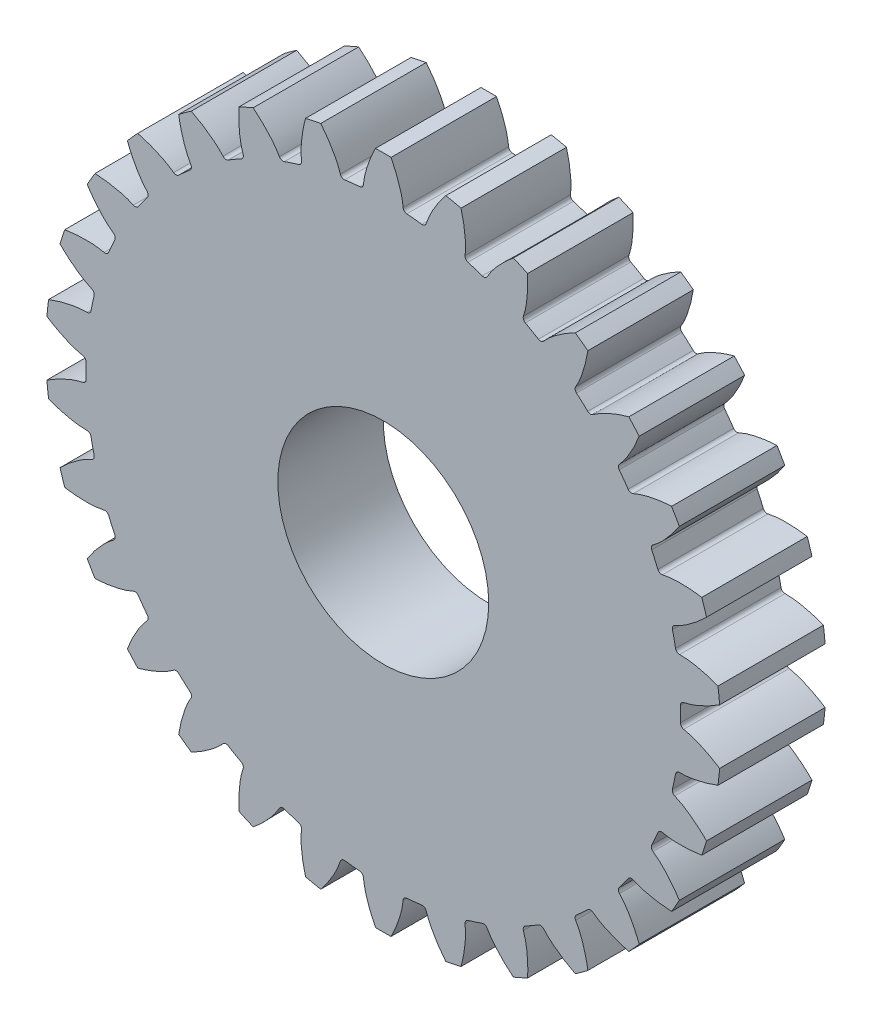
SolidWorks part; units mm, degrees
ref_plane "前视基准面" through (0, 0, 0) normal (0, 0, 1) x (1, 0, 0)
ref_plane "上视基准面" through (0, 0, 0) normal (0, 1, 0) x (1, 0, 0)
ref_plane "右视基准面" through (0, 0, 0) normal (1, 0, 0) x (0, 0, -1)
other "Configuration Table"
sketch "circles" plane through (0, 0, 0) normal (0, 0, 1) x (1, 0, 0)
  circle A0 centre (0, 0) radius 32
  circle A1 centre (0, 0) radius 27.5
  circle A2 centre (0, 0) radius 28.1908
  circle A3 centre (0, 0) radius 30
  dimension "D1" = 60
  dimension "D2" = 56.3816
  dimension "D3" = 55
  dimension "D4" = 64
extrude "Gear_extrude" add sketch "circles" along normal blind 10 contours A0
sketch "Involute" plane through (0, 0, 10) normal (0, 0, 1) x (1, 0, 0)
  spline S0 degree 4 poles (28.171, -1.0557) (28.2223, -1.0593) (28.3658, -1.0748) (28.6344, -1.1247) (29.0665, -1.2353) (29.6059, -1.4183) (30.2862, -1.7021) (31.0629, -2.0956) (31.8862, -2.5882) (32.9602, -3.3359) (34.1728, -4.337) (35.451, -5.5998) (36.7769, -7.1739) (37.9681, -8.8517) (39.0285, -10.6149) (39.9764, -12.4839) (40.7958, -14.4124) (41.4038, -16.142) (41.8493, -17.6484) (42.1713, -18.9171) (42.3998, -19.9389) (42.6495, -21.2237) (42.8522, -22.517) (43.0089, -23.8165) (43.1207, -25.1207) (43.1836, -26.1655) (43.2157, -27.0819) (43.2272, -27.8657) (43.226, -28.5232) (43.2194, -29.0333) (43.2013, -29.7091) (43.1793, -30.2472) (43.1275, -31.2203) (43.075, -31.832) (43.0114, -32.5795) (42.9682, -32.9515) (42.9431, -33.1951) (42.9309, -33.297) knots 0 0 0 0 0 0.005377 0.015084 0.028532 0.04661 0.064855 0.092111 0.119476 0.146842 0.201575 0.256307 0.307035 0.361767 0.4165 0.471232 0.525964 0.580697 0.608063 0.635429 0.662795 0.690161 0.744894 0.77226 0.799626 0.826992 0.854358 0.868042 0.881725 0.895408 0.909091 0.931818 0.954545 0.977273 0.988636 1 1 1 1 1 construction
  spline S2 degree 4 poles (28.171, 1.0557) (28.2223, 1.0593) (28.3658, 1.0748) (28.6344, 1.1247) (29.0665, 1.2353) (29.6059, 1.4183) (30.2862, 1.7021) (31.0629, 2.0956) (31.8862, 2.5882) (32.9602, 3.3359) (34.1728, 4.337) (35.451, 5.5998) (36.7769, 7.1739) (37.9681, 8.8517) (39.0285, 10.6149) (39.9764, 12.4839) (40.7958, 14.4124) (41.4038, 16.142) (41.8493, 17.6484) (42.1713, 18.9171) (42.3998, 19.9389) (42.6495, 21.2237) (42.8522, 22.517) (43.0089, 23.8165) (43.1207, 25.1207) (43.1836, 26.1655) (43.2157, 27.0819) (43.2272, 27.8657) (43.226, 28.5232) (43.2194, 29.0333) (43.2013, 29.7091) (43.1793, 30.2472) (43.1275, 31.2203) (43.075, 31.832) (43.0114, 32.5795) (42.9682, 32.9515) (42.9431, 33.1951) (42.9309, 33.297) knots 0 0 0 0 0 0.005377 0.015084 0.028532 0.04661 0.064855 0.092111 0.119476 0.146842 0.201575 0.256307 0.307035 0.361767 0.4165 0.471232 0.525964 0.580697 0.608063 0.635429 0.662795 0.690161 0.744894 0.77226 0.799626 0.826992 0.854358 0.868042 0.881725 0.895408 0.909091 0.931818 0.954545 0.977273 0.988636 1 1 1 1 1 construction
  spline S3 degree 4 poles (28.171, 1.0557) (28.2223, 1.0593) (28.3658, 1.0748) (28.6344, 1.1247) (29.0665, 1.2353) (29.6059, 1.4183) (30.2862, 1.7021) (31.0629, 2.0956) (31.8862, 2.5882) (32.9602, 3.3359) (34.1728, 4.337) (35.451, 5.5998) (36.7769, 7.1739) (37.9681, 8.8517) (39.0285, 10.6149) (39.9764, 12.4839) (40.7958, 14.4124) (41.4038, 16.142) (41.8493, 17.6484) (42.1713, 18.9171) (42.3998, 19.9389) (42.6495, 21.2237) (42.8522, 22.517) (43.0089, 23.8165) (43.1207, 25.1207) (43.1836, 26.1655) (43.2157, 27.0819) (43.2272, 27.8657) (43.226, 28.5232) (43.2194, 29.0333) (43.2078, 29.4683) (43.1997, 29.7103) (43.1953, 29.8292) knots 0 0 0 0 0 0.005377 0.015084 0.028532 0.04661 0.064855 0.092111 0.119476 0.146842 0.201575 0.256307 0.307035 0.361767 0.4165 0.471232 0.525964 0.580697 0.608063 0.635429 0.662795 0.690161 0.744894 0.77226 0.799626 0.826992 0.854358 0.868042 0.881725 0.895408 0.909091 0.909091 0.909091 0.909091 0.909091
  spline S4 degree 4 poles (28.171, -1.0557) (28.2223, -1.0593) (28.3658, -1.0748) (28.6344, -1.1247) (29.0665, -1.2353) (29.6059, -1.4183) (30.2862, -1.7021) (31.0629, -2.0956) (31.8862, -2.5882) (32.9602, -3.3359) (34.1728, -4.337) (35.451, -5.5998) (36.7769, -7.1739) (37.9681, -8.8517) (39.0285, -10.6149) (39.9764, -12.4839) (40.7958, -14.4124) (41.4038, -16.142) (41.8493, -17.6484) (42.1713, -18.9171) (42.3998, -19.9389) (42.6495, -21.2237) (42.8522, -22.517) (43.0089, -23.8165) (43.1207, -25.1207) (43.1836, -26.1655) (43.2157, -27.0819) (43.2272, -27.8657) (43.226, -28.5232) (43.2194, -29.0333) (43.2078, -29.4683) (43.1997, -29.7103) (43.1953, -29.8292) knots 0 0 0 0 0 0.005377 0.015084 0.028532 0.04661 0.064855 0.092111 0.119476 0.146842 0.201575 0.256307 0.307035 0.361767 0.4165 0.471232 0.525964 0.580697 0.608063 0.635429 0.662795 0.690161 0.744894 0.77226 0.799626 0.826992 0.854358 0.868042 0.881725 0.895408 0.909091 0.909091 0.909091 0.909091 0.909091
sketch "Db>Df" plane through (0, 0, 10) normal (0, 0, 1) x (1, 0, 0)
  line L2 (0, 0) -> (29.9589, 1.5701) construction
  line L3 (0, 0) -> (60.2478, -1.5776) construction
  line L4 (43.1953, 29.8292) -> (60.2478, -1.5776)
  line L5 (60.2478, -1.5776) -> (43.1953, -29.8292)
  circle A2 centre (0, 0) radius 30 construction
  circle A3 centre (0, 0) radius 28.1908 construction
  arc A4 (28.171, -1.0557) -> (28.171, 1.0557) centre (0, 0) ccw
  spline S0 degree 4 poles (-58.7454, -1999.1168) (17.076, -52.2104) (22.5891, -1.8433) (25.9954, -0.4491) (29.0665, -1.2353) (29.6059, -1.4183) (30.2862, -1.7021) (31.0629, -2.0956) (31.8862, -2.5882) (32.9602, -3.3359) (34.1728, -4.337) (35.451, -5.5998) (36.7769, -7.1739) (37.9681, -8.8517) (39.0285, -10.6149) (39.9764, -12.4839) (40.7958, -14.4124) (41.4038, -16.142) (41.8493, -17.6484) (42.1713, -18.9171) (42.3998, -19.9389) (42.6495, -21.2237) (42.8522, -22.517) (43.0089, -23.8165) (43.1207, -25.1207) (43.1836, -26.1655) (43.2157, -27.0819) (43.2272, -27.8657) (43.226, -28.5232) (43.1903, -31.2711) (42.8434, -36.3545) (44.7406, 23.1759) (-32.5965, -2028.0551) knots -0.284666 -0.284666 -0.284666 -0.284666 -0.284666 0.005377 0.015084 0.028532 0.04661 0.064855 0.092111 0.119476 0.146842 0.201575 0.256307 0.307035 0.361767 0.4165 0.471232 0.525964 0.580697 0.608063 0.635429 0.662795 0.690161 0.744894 0.77226 0.799626 0.826992 0.854358 0.868042 0.881725 0.895408 1.149228 1.149228 1.149228 1.149228 1.149228 only from (28.171, -1.0557) to (43.1953, -29.8292) construction
  spline S1 degree 4 poles (-58.7454, 1999.1168) (17.076, 52.2104) (22.5891, 1.8433) (25.9954, 0.4491) (29.0665, 1.2353) (29.6059, 1.4183) (30.2862, 1.7021) (31.0629, 2.0956) (31.8862, 2.5882) (32.9602, 3.3359) (34.1728, 4.337) (35.451, 5.5998) (36.7769, 7.1739) (37.9681, 8.8517) (39.0285, 10.6149) (39.9764, 12.4839) (40.7958, 14.4124) (41.4038, 16.142) (41.8493, 17.6484) (42.1713, 18.9171) (42.3998, 19.9389) (42.6495, 21.2237) (42.8522, 22.517) (43.0089, 23.8165) (43.1207, 25.1207) (43.1836, 26.1655) (43.2157, 27.0819) (43.2272, 27.8657) (43.226, 28.5232) (43.1903, 31.2711) (42.8434, 36.3545) (44.7406, -23.1759) (-32.5965, 2028.0551) knots -0.284666 -0.284666 -0.284666 -0.284666 -0.284666 0.005377 0.015084 0.028532 0.04661 0.064855 0.092111 0.119476 0.146842 0.201575 0.256307 0.307035 0.361767 0.4165 0.471232 0.525964 0.580697 0.608063 0.635429 0.662795 0.690161 0.744894 0.77226 0.799626 0.826992 0.854358 0.868042 0.881725 0.895408 1.149228 1.149228 1.149228 1.149228 1.149228 only from (28.171, 1.0557) to (43.1953, 29.8292) construction
  spline S2 degree 4 poles (28.171, -1.0557) (28.2223, -1.0593) (28.3658, -1.0748) (28.6344, -1.1247) (29.0665, -1.2353) (29.6059, -1.4183) (30.2862, -1.7021) (31.0629, -2.0956) (31.8862, -2.5882) (32.9602, -3.3359) (34.1728, -4.337) (35.451, -5.5998) (36.7769, -7.1739) (37.9681, -8.8517) (39.0285, -10.6149) (39.9764, -12.4839) (40.7958, -14.4124) (41.4038, -16.142) (41.8493, -17.6484) (42.1713, -18.9171) (42.3998, -19.9389) (42.6495, -21.2237) (42.8522, -22.517) (43.0089, -23.8165) (43.1207, -25.1207) (43.1836, -26.1655) (43.2157, -27.0819) (43.2272, -27.8657) (43.226, -28.5232) (43.2194, -29.0333) (43.2078, -29.4683) (43.1997, -29.7103) (43.1953, -29.8292) knots 0 0 0 0 0 0.005377 0.015084 0.028532 0.04661 0.064855 0.092111 0.119476 0.146842 0.201575 0.256307 0.307035 0.361767 0.4165 0.471232 0.525964 0.580697 0.608063 0.635429 0.662795 0.690161 0.744894 0.77226 0.799626 0.826992 0.854358 0.868042 0.881725 0.895408 0.909091 0.909091 0.909091 0.909091 0.909091
  spline S3 degree 4 poles (28.171, 1.0557) (28.2223, 1.0593) (28.3658, 1.0748) (28.6344, 1.1247) (29.0665, 1.2353) (29.6059, 1.4183) (30.2862, 1.7021) (31.0629, 2.0956) (31.8862, 2.5882) (32.9602, 3.3359) (34.1728, 4.337) (35.451, 5.5998) (36.7769, 7.1739) (37.9681, 8.8517) (39.0285, 10.6149) (39.9764, 12.4839) (40.7958, 14.4124) (41.4038, 16.142) (41.8493, 17.6484) (42.1713, 18.9171) (42.3998, 19.9389) (42.6495, 21.2237) (42.8522, 22.517) (43.0089, 23.8165) (43.1207, 25.1207) (43.1836, 26.1655) (43.2157, 27.0819) (43.2272, 27.8657) (43.226, 28.5232) (43.2194, 29.0333) (43.2078, 29.4683) (43.1997, 29.7103) (43.1953, 29.8292) knots 0 0 0 0 0 0.005377 0.015084 0.028532 0.04661 0.064855 0.092111 0.119476 0.146842 0.201575 0.256307 0.307035 0.361767 0.4165 0.471232 0.525964 0.580697 0.608063 0.635429 0.662795 0.690161 0.744894 0.77226 0.799626 0.826992 0.854358 0.868042 0.881725 0.895408 0.909091 0.909091 0.909091 0.909091 0.909091
  dimension "D1" = 4.5
  dimension "D2" = 60
extrude "extruded-cut1" cut sketch "Db>Df" against normal through all
fillet "fillet1" radius 0.38 2 edges at (28.171, -1.0557, 5) (28.171, 1.0557, 5)
pattern_circular "circular-parttern1" count 30 over 360 about axis through (0, 0, 10) along (0, 0, -1) of "extruded-cut1", "fillet1" reverse direction yes
sketch "Db<Df" [suppressed] plane through (0, 0, 10) normal (0, 0, 1) x (1, 0, 0)
  line L0 (0, 0) -> (100.8439, 0) construction
  line L1 (0, 0) -> (49.9753, 1.5705) construction
  line L2 (73.0175, 48.1968) -> (100.8439, 0)
  line L3 (100.8439, 0) -> (73.0175, -48.1968)
  circle A0 centre (0, 0) radius 47.5 construction
  arc A1 (47.4927, -0.8355) -> (47.4927, 0.8355) centre (0, 0) ccw
  circle A2 centre (0, 0) radius 50 construction
  spline S0 degree 4 poles (69.1798, -1998.5936) (37.8966, 59.197) (41.8514, 1.7937) (44.8419, 0.3903) (47.7946, 0.8837) (48.4767, 1.0444) (49.3818, 1.3297) (50.5254, 1.7793) (51.8333, 2.4075) (53.2224, 3.1999) (54.6746, 4.1663) (56.0658, 5.2211) (57.3956, 6.3522) (58.6648, 7.5507) (60.1325, 9.0778) (61.7919, 11.0209) (63.5752, 13.4244) (65.4038, 16.3254) (67.0485, 19.4065) (68.4812, 22.5914) (69.5546, 25.4522) (70.3495, 27.9469) (70.9303, 30.0495) (71.3467, 31.7445) (71.7156, 33.4497) (72.0375, 35.1657) (72.3133, 36.8876) (72.5435, 38.6195) (72.7289, 40.3511) (72.8524, 41.8792) (72.9313, 43.1759) (72.9787, 44.2811) (73.0067, 45.1233) (73.0226, 46.0516) (73.0565, 49.344) (72.7733, 58.0548) (73.7264, -18.7455) (39.1601, 2047.4863) knots -0.159153 -0.159153 -0.159153 -0.159153 -0.159153 0.002688 0.005377 0.015084 0.028532 0.04661 0.064855 0.092111 0.119476 0.146842 0.174209 0.201575 0.228941 0.256307 0.307035 0.361767 0.4165 0.471232 0.525964 0.580697 0.608063 0.635429 0.662795 0.690161 0.717528 0.744894 0.77226 0.799626 0.826992 0.840675 0.854358 0.868042 0.881725 0.895408 1.086914 1.086914 1.086914 1.086914 1.086914 only from (46.9782, 0.7758) to (73.0175, 48.1968) construction
  spline S1 degree 4 poles (47.4927, 0.8355) (47.602, 0.8537) (47.9217, 0.9139) (48.5186, 1.0576) (49.3818, 1.3297) (50.5254, 1.7793) (51.8333, 2.4075) (53.2224, 3.1999) (54.6746, 4.1663) (56.0658, 5.2211) (57.3956, 6.3522) (58.6648, 7.5507) (60.1325, 9.0778) (61.7919, 11.0209) (63.5752, 13.4244) (65.4038, 16.3254) (67.0485, 19.4065) (68.4812, 22.5914) (69.5546, 25.4522) (70.3495, 27.9469) (70.9303, 30.0495) (71.3467, 31.7445) (71.7156, 33.4497) (72.0375, 35.1657) (72.3133, 36.8876) (72.5435, 38.6195) (72.7289, 40.3511) (72.8524, 41.8792) (72.9313, 43.1759) (72.9787, 44.2811) (73.0067, 45.1233) (73.0226, 46.0516) (73.0306, 46.8265) (73.0255, 47.605) (73.0207, 47.9985) (73.0175, 48.1968) knots 0.008127 0.008127 0.008127 0.008127 0.008127 0.015084 0.028532 0.04661 0.064855 0.092111 0.119476 0.146842 0.174209 0.201575 0.228941 0.256307 0.307035 0.361767 0.4165 0.471232 0.525964 0.580697 0.608063 0.635429 0.662795 0.690161 0.717528 0.744894 0.77226 0.799626 0.826992 0.840675 0.854358 0.868042 0.881725 0.895408 0.909091 0.909091 0.909091 0.909091 0.909091
  spline S2 degree 4 poles (69.1798, 1998.5936) (37.8966, -59.197) (41.8514, -1.7937) (44.8419, -0.3903) (47.7946, -0.8837) (48.4767, -1.0444) (49.3818, -1.3297) (50.5254, -1.7793) (51.8333, -2.4075) (53.2224, -3.1999) (54.6746, -4.1663) (56.0658, -5.2211) (57.3956, -6.3522) (58.6648, -7.5507) (60.1325, -9.0778) (61.7919, -11.0209) (63.5752, -13.4244) (65.4038, -16.3254) (67.0485, -19.4065) (68.4812, -22.5914) (69.5546, -25.4522) (70.3495, -27.9469) (70.9303, -30.0495) (71.3467, -31.7445) (71.7156, -33.4497) (72.0375, -35.1657) (72.3133, -36.8876) (72.5435, -38.6195) (72.7289, -40.3511) (72.8524, -41.8792) (72.9313, -43.1759) (72.9787, -44.2811) (73.0067, -45.1233) (73.0226, -46.0516) (73.0565, -49.344) (72.7733, -58.0548) (73.7264, 18.7455) (39.1601, -2047.4863) knots -0.159153 -0.159153 -0.159153 -0.159153 -0.159153 0.002688 0.005377 0.015084 0.028532 0.04661 0.064855 0.092111 0.119476 0.146842 0.174209 0.201575 0.228941 0.256307 0.307035 0.361767 0.4165 0.471232 0.525964 0.580697 0.608063 0.635429 0.662795 0.690161 0.717528 0.744894 0.77226 0.799626 0.826992 0.840675 0.854358 0.868042 0.881725 0.895408 1.086914 1.086914 1.086914 1.086914 1.086914 only from (46.9782, -0.7758) to (73.0175, -48.1968) construction
  spline S3 degree 4 poles (47.4927, -0.8355) (47.602, -0.8537) (47.9217, -0.9139) (48.5186, -1.0576) (49.3818, -1.3297) (50.5254, -1.7793) (51.8333, -2.4075) (53.2224, -3.1999) (54.6746, -4.1663) (56.0658, -5.2211) (57.3956, -6.3522) (58.6648, -7.5507) (60.1325, -9.0778) (61.7919, -11.0209) (63.5752, -13.4244) (65.4038, -16.3254) (67.0485, -19.4065) (68.4812, -22.5914) (69.5546, -25.4522) (70.3495, -27.9469) (70.9303, -30.0495) (71.3467, -31.7445) (71.7156, -33.4497) (72.0375, -35.1657) (72.3133, -36.8876) (72.5435, -38.6195) (72.7289, -40.3511) (72.8524, -41.8792) (72.9313, -43.1759) (72.9787, -44.2811) (73.0067, -45.1233) (73.0226, -46.0516) (73.0306, -46.8265) (73.0255, -47.605) (73.0207, -47.9985) (73.0175, -48.1968) knots 0.008127 0.008127 0.008127 0.008127 0.008127 0.015084 0.028532 0.04661 0.064855 0.092111 0.119476 0.146842 0.174209 0.201575 0.228941 0.256307 0.307035 0.361767 0.4165 0.471232 0.525964 0.580697 0.608063 0.635429 0.662795 0.690161 0.717528 0.744894 0.77226 0.799626 0.826992 0.840675 0.854358 0.868042 0.881725 0.895408 0.909091 0.909091 0.909091 0.909091 0.909091
  dimension "D1" = 3
  dimension "D2" = 60
extrude "extruded-cut2" [suppressed] cut sketch "Db<Df" against normal through all
fillet "fillet2" [suppressed] radius 0.38
pattern_circular "circular-parttern2" [suppressed] count 30 over 360 of bodies 109
sketch "Sketch1" plane through (0, 0, 0) normal (0, 0, 1) x (1, 0, 0)
  circle A0 centre (0, 0) radius 10
extrude "Cut-Extrude1" cut sketch "Sketch1" along normal blind 10
ref_plane "gear_mid_plane" through (0, 0, 0) normal (0, 0, 1) x (1, 0, 0)
ref_plane "front_face" through (0, 0, 10) normal (0, 0, 1) x (1, 0, 0)
ref_plane "back_face" through (0, 0, 0) normal (0, 0, 1) x (1, 0, 0)
sketch3d "3DSketch1"
  line L0 (0, 0, 0) -> (0, 0, 10) construction
ref_axis "shaft_axis" through (0, 0, 0) along (0, 0, 1)
equation "\"M\" = 2mm"
equation "\"Z\" = 30"
equation "\"B\" = 10mm"
equation "\"Alpha\"= 20\t'压力角"
equation "\"D\"= \"M\"*\"Z\"   '分度圆"
equation "\"Db\"= \"D\" * cos ( \"Alpha\" )  \t'基圆"
equation "\"Hax\" = 1"
equation "\"Cx\" = 0.25"
equation "\"Ha\"= \"Hax\" * \"M\"\t'齿顶高"
equation "\"Hf\"= ( \"Hax\" + \"Cx\" ) * \"M\"\t'齿根高"
equation "\"Df\"= \"D\" - 2 * \"Hf\"\t\t'齿根圆"
equation "\"Da\"= \"D\" + 2 * \"Ha\"\t'齿顶圆"
equation "\"Theta\"= 360 * sqr ( ( 1 / cos ( \"Alpha\" ) ) ^ 2 - 1 ) / ( 2 * pi ) - atn ( sqr ( ( 1 / cos ( \"Alpha\" ) ) ^ 2 - 1 ) )"
equation "\"Phi\"= - ( 2 * pi * ( 90 / \"Z\" - \"Theta\" ) / 360 )"
equation "\"D1@circles\" = \"D\""
equation "\"D2@circles\" = \"Db\""
equation "\"D3@circles\" = \"Df\""
equation "\"D4@circles\" = \"Da\""
equation "\"D1@Gear_extrude\" = \"B\""
equation "\"D1@circular-parttern1\" = \"Z\""
equation "\"Db>Df\"= IIF ( \"Db\" > \"Df\" ,  unsuppressed  ,  suppressed  ) "
equation "\"extruded-cut1\"= IIF ( \"Db\" > \"Df\" ,  unsuppressed  ,  suppressed  ) "
equation "\"D1@Db<Df\"=90/\"Z\""
equation "\"D1@fillet1\" = 0.19 * \"M\""
equation "\"Db<Df\" = IIF ( \"Db\" < \"Df\" , \"unsuppressed\" , \"suppressed\" )"
equation "\"extruded-cut2\"= IIF ( \"Db\" < \"Df\" ,  unsuppressed  ,  suppressed  ) "
equation "\"D1@fillet2\" = 0.19 * \"M\""
equation "\"D1@circular-parttern2\" = \"Z\""
equation "\"circular-parttern2\"= IIF ( \"Db\" < \"Df\" ,  unsuppressed  ,  suppressed  ) "
equation "\"fillet1\"= IIF ( \"Db\" > \"Df\" ,  unsuppressed  ,  suppressed  ) "
equation "\"fillet2\"= IIF ( \"Db\" < \"Df\" ,  unsuppressed  ,  suppressed  ) "
equation "\"circular-parttern1\"= IIF ( \"Db\" > \"Df\" , \"unsuppressed\" , \"suppressed\" )"
